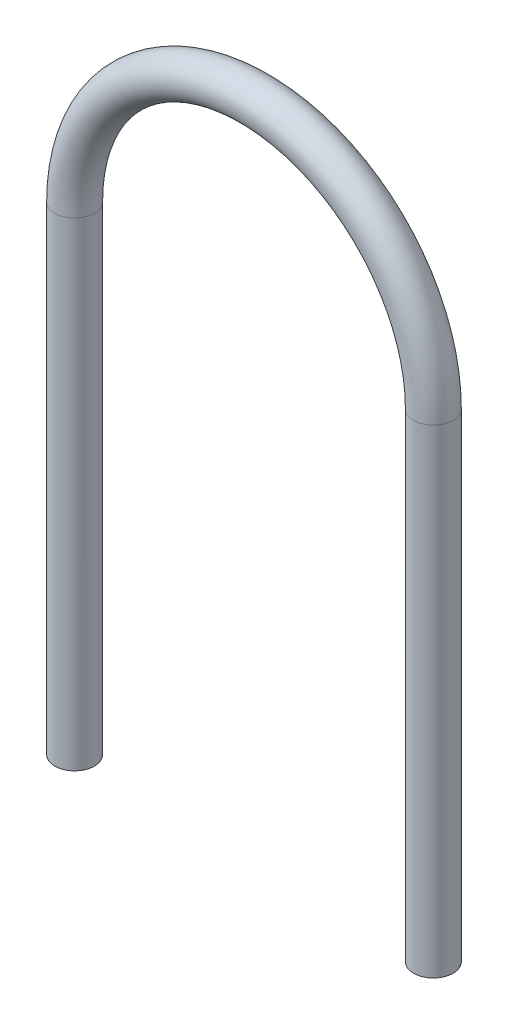
SolidWorks part; units mm, degrees
material "AISI 1020"
ref_plane "Front Plane" through (0, 0, 0) normal (0, 0, 1) x (1, 0, 0)
ref_plane "Top Plane" through (0, 0, 0) normal (0, 1, 0) x (1, 0, 0)
ref_plane "Right Plane" through (0, 0, 0) normal (1, 0, 0) x (0, 0, -1)
sketch "Sketch1" plane through (0, 0, 0) normal (0, 0, 1) x (1, 0, 0)
  line L0 (0, 0) -> (0, 76.2)
  line L1 (-50.8, 76.2) -> (-50.8, 0)
  arc A0 (0, 76.2) -> (-50.8, 76.2) centre (-25.4, 76.2) ccw
  dimension "D1" = 25.4
sketch "Sketch2" plane through (0, 0, 0) normal (0, 1, 0) x (1, 0, 0)
  line L0 (0, 0) -> (3.1496, 0) construction
  circle A0 centre (3.1496, 0) radius 3.1496
sweep "Sweep1" add profiles "Sketch2" path "Sketch1"
